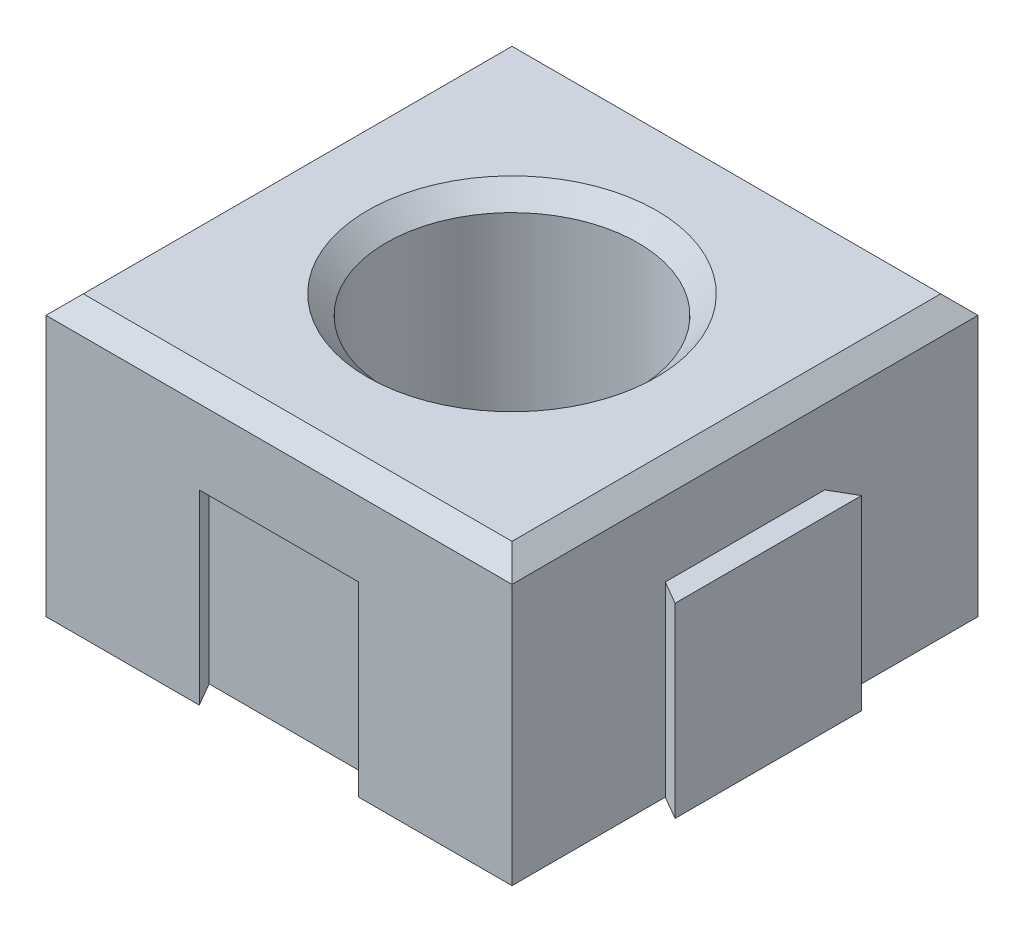
SolidWorks part; units mm, degrees
ref_plane "Front Plane" through (0, 0, 0) normal (0, 0, 1) x (1, 0, 0)
ref_plane "Top Plane" through (0, 0, 0) normal (0, 1, 0) x (1, 0, 0)
ref_plane "Right Plane" through (0, 0, 0) normal (1, 0, 0) x (0, 0, -1)
sketch "Sketch1" plane through (0, 0, 0) normal (0, 1, 0) x (1, 0, 0)
  line L1 (0, 0) -> (50, 0)
  line L2 (0, 0) -> (0, 50)
  line L3 (0, 50) -> (50, 50)
  line L4 (50, 0) -> (50, 50)
  dimension "D1" = 50
extrude "Boss-Extrude1" add sketch "Sketch1" along normal blind 30
sketch "Sketch2" plane through (0, 30, 0) normal (0, 1, 0) x (1, 0, 0)
  line L0 (0, 0) -> (50, 50) construction
  line L1 (0, 50) -> (50, 0) construction
  circle A0 centre (25, 25) radius 13.5
  dimension "D1" = 27
extrude "Cut-Extrude1" cut sketch "Sketch2" against normal blind 26
sketch "Sketch3" plane through (0, 0, 0) normal (0, 1, 0) x (1, 0, 0)
  line L0 (50, 33.5566) -> (52.5, 35)
  line L1 (50, 0) -> (50, 50) construction
  line L2 (52.5, 35) -> (52.5, 15)
  line L3 (52.5, 15) -> (50, 16.4434)
  line L4 (50, 25) -> (52.5, 25) construction
  line L5 (16.4434, 50) -> (15, 52.5)
  line L6 (50, 50) -> (0, 50) construction
  line L7 (15, 52.5) -> (35, 52.5)
  line L8 (35, 52.5) -> (33.5566, 50)
  line L9 (25, 52.5) -> (25, 50) construction
  line L10 (0, 33.5566) -> (2.5, 35)
  line L11 (0, 50) -> (0, 0) construction
  line L12 (2.5, 35) -> (2.5, 15)
  line L13 (2.5, 15) -> (0, 16.4434)
  line L14 (0, 25) -> (2.5, 25) construction
  line L15 (16.4434, 0) -> (15, 2.5)
  line L16 (0, 0) -> (50, 0) construction
  line L17 (15, 2.5) -> (35, 2.5)
  line L18 (35, 2.5) -> (33.5566, 0)
  line L19 (25, 0) -> (25, 2.5) construction
  line L20 (50, 16.4434) -> (50, 33.5566)
  line L21 (33.5566, 50) -> (16.4434, 50)
  line L22 (0, 33.5566) -> (0, 16.4434)
  line L23 (16.4434, 0) -> (33.5566, 0)
  point P8 (50, 25)
  dimension "D2" = 60
  dimension "D3" = 2.5
  dimension "D4" = 20
extrude "Boss-Extrude2" add sketch "Sketch3" along normal blind 20 contours L2 L3 L20 L0
extrude "Boss-Extrude3" add sketch "Sketch3<3>" along normal blind 20 contours L7 L8 L21 L5
sketch "Sketch3<3>" plane through (0, 0, 0) normal (0, 1, 0) x (1, 0, 0) same geometry as "Sketch3"
extrude "Cut-Extrude2" cut sketch "Sketch3<4>" along normal blind 20 contours L12 L13 L22 L10
sketch "Sketch3<4>" plane through (0, 0, 0) normal (0, 1, 0) x (1, 0, 0) same geometry as "Sketch3"
extrude "Cut-Extrude3" cut sketch "Sketch3<5>" along normal blind 20 contours L17 L18 L23 L15
sketch "Sketch3<5>" plane through (0, 0, 0) normal (0, 1, 0) x (1, 0, 0) same geometry as "Sketch3"
chamfer "Chamfer1" distance 2 angle 45 5 edges at (25, 30, -50) (50, 30, -25) (25, 30, 0) (0, 30, -25) (25, 30, -11.5)
